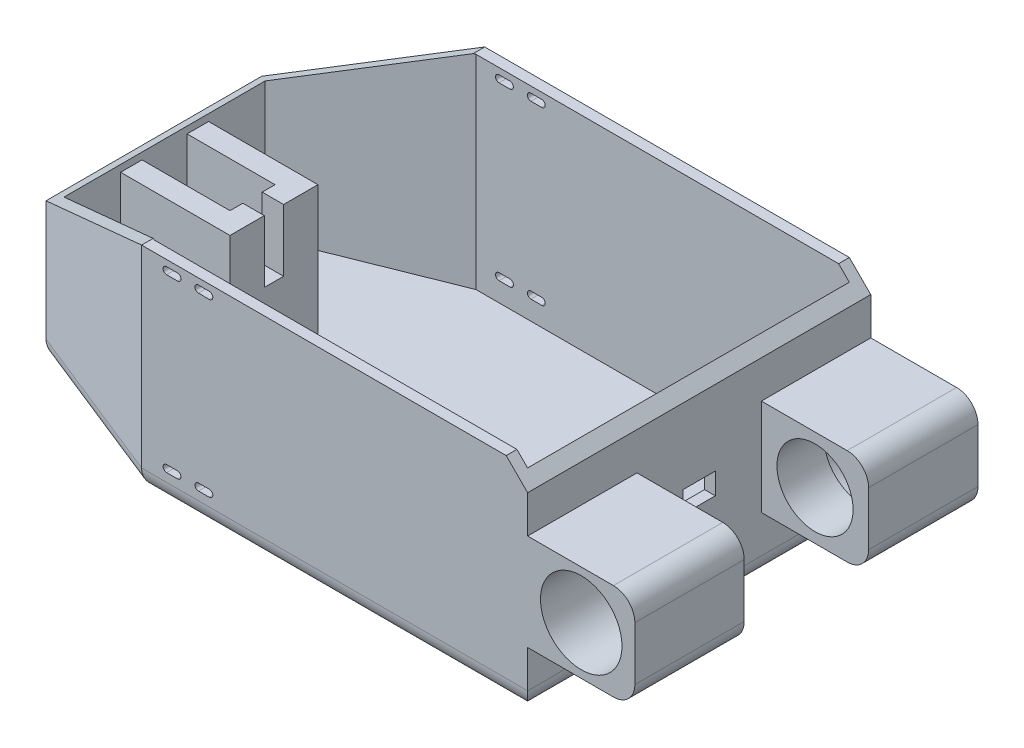
SolidWorks part; units mm, degrees
material "Silicon"
ref_plane "Front Plane" through (0, 0, 0) normal (0, 0, 1) x (1, 0, 0)
ref_plane "Top Plane" through (0, 0, 0) normal (0, 1, 0) x (1, 0, 0)
ref_plane "Right Plane" through (0, 0, 0) normal (1, 0, 0) x (0, 0, -1)
sketch "Sketch2" plane through (0, 0, 0) normal (0, 1, 0) x (1, 0, 0)
  line L0 (-11.9102, -80) -> (-11.9102, 80)
  line L1 (-11.9102, 0) -> (-266.1883, 0) construction
  line L2 (-11.9102, 0) -> (-191.9102, 0) construction
  line L4 (-191.9102, 80) -> (-11.9102, 80)
  line L5 (-11.9102, -80) -> (-191.9102, -80)
  line L6 (-266.1883, -50.2887) -> (-266.1883, 50.2887)
  line L9 (-266.1883, 50.2887) -> (-191.9102, 80)
  line L10 (-266.1883, -50.2887) -> (-191.9102, -80)
  point P3 (-11.9102, 0)
  point P10 (-191.9102, 0)
  point P13 (-266.1883, 0)
extrude "Boss-Extrude1" add sketch "Sketch2" along normal blind 100
shell "Shell1" thickness 5 removed face at (-156.6696, 100, 0)
chamfer "Chamfer1" distance 10 angle 45 1 edges at (-11.9102, 100, 0)
chamfer "Chamfer2" distance 10 angle 45 1 edges at (-266.1883, 100, 0)
fillet "Fillet2" radius 10 6 edges at (-11.9102, 0, 0) (-101.9102, 0, -80) (-229.0493, 0, -65.1444) (-266.1883, 0, 0) (-229.0493, 0, 65.1444) (-101.9102, 0, 80)
sketch "Sketch3" plane through (0, 0, 80) normal (0, 0, 1) x (1, 0, 0)
  line L0 (-191.9102, 100) -> (-266.1883, 65.8911)
  line L1 (-266.1883, 90) -> (-266.1883, 10) construction
  line L2 (-266.1883, 65.8911) -> (-266.1883, 100)
  line L3 (-266.1883, 100) -> (-191.9102, 100)
extrude "Cut-Extrude1" cut sketch "Sketch3" against normal blind 250
sketch "Sketch4" plane through (0, 5, 0) normal (0, 1, 0) x (1, 0, 0)
  line L1 (-261.1883, 46.9036) -> (-261.1883, -46.9036) construction
  line L2 (-261.1883, 10.5) -> (-220.1883, 10.5)
  line L3 (-220.1883, 10.5) -> (-220.1883, -10.5)
  line L4 (-220.1883, -10.5) -> (-384.7778, -10.5)
  line L5 (-215.1883, -15.5) -> (-444.0517, -15.5)
  line L7 (-261.6101, 15.5) -> (-215.1883, 15.5)
  line L8 (-215.1883, 15.5) -> (-215.1883, -15.5)
  line L9 (-384.7778, -10.5) -> (-261.1883, 10.5) construction
  line L10 (-261.1883, 10.5) -> (-384.7778, 9.5024)
  line L11 (-384.7778, 9.5024) -> (-384.7778, -10.5)
  line L12 (-261.6101, 15.5) -> (-444.0517, 15.5)
  line L13 (-444.0517, -15.5) -> (-261.6101, 15.5) construction
  line L14 (-444.0517, 15.5) -> (-444.0517, -15.5)
  point P5 (-336.9102, 0)
  dimension "D2" = 41
  dimension "D3" = 21
extrude "Boss-Extrude5" add sketch "Sketch4" along normal blind 60
sketch "Sketch8" plane through (0, 5, 0) normal (0, 1, 0) x (1, 0, 0)
  line L1 (-220.1883, 10.5) -> (-261.1883, 10.5)
  line L2 (-220.1883, 10.5) -> (-220.1883, -10.5)
  line L3 (-220.1883, -10.5) -> (-261.1883, -10.5)
  line L4 (-261.1883, 10.5) -> (-261.1883, -10.5)
  line L5 (-220.1883, 10.5) -> (-261.1883, -10.5) construction
  line L6 (-220.1883, -10.5) -> (-261.1883, 10.5) construction
  point P4 (-240.6883, 0)
extrude "Boss-Extrude6" add sketch "Sketch8" along normal blind 31
sketch "Sketch12" plane through (-11.9102, 0, 0) normal (1, 0, 0) x (0, 0, -1)
  line L0 (0, 90) -> (0, 10) construction
  line L1 (80, 90) -> (-80, 90) construction
  line L2 (-80, 10) -> (80, 10) construction
  line L3 (-80, 50) -> (80, 50) construction
  line L4 (80, 90) -> (80, 10) construction
  line L5 (-80, 27.5) -> (-80, 72.5)
  line L6 (-80, 90) -> (-80, 10) construction
  line L7 (-80, 72.5) -> (-29, 72.5)
  line L8 (-29, 72.5) -> (-29, 27.5)
  line L9 (-29, 27.5) -> (-80, 27.5)
  point P11 (0, 50)
  point P16 (-80, 50)
  dimension "D1" = 51
  dimension "D2" = 45
extrude "Boss-Extrude7" add sketch "Sketch12" along normal blind 50
sketch "Sketch26" plane through (0, 0, 80) normal (0, 0, 1) x (1, 0, 0)
  line L0 (13.0898, 27.5) -> (13.0898, 72.5) construction
  line L1 (38.0898, 27.5) -> (-11.9102, 27.5) construction
  line L2 (38.0898, 72.5) -> (-11.9102, 72.5) construction
  line L3 (-11.9102, 50) -> (38.0898, 50) construction
  line L4 (38.0898, 72.5) -> (38.0898, 27.5) construction
  circle A0 centre (13.0898, 50) radius 19
  point P11 (13.0898, 50)
  dimension "D1" = 38
extrude "Cut-Extrude2" cut sketch "Sketch26" against normal blind 29
sketch "Sketch28" plane through (0, 0, 51) normal (0, 0, 1) x (1, 0, 0)
  line L0 (13.0898, 72.5) -> (13.0898, 27.5) construction
  line L1 (38.0898, 72.5) -> (-11.9102, 72.5) construction
  line L2 (38.0898, 27.5) -> (-11.9102, 27.5) construction
  line L3 (-11.9102, 50) -> (38.0898, 50) construction
  line L4 (38.0898, 72.5) -> (38.0898, 27.5) construction
  circle A0 centre (13.0898, 50) radius 17.75
  point P11 (13.0898, 50)
  dimension "D1" = 35.5
extrude "Cut-Extrude3" cut sketch "Sketch28" against normal blind 22
mirror "Mirror1" about plane through (0, 0, 0) normal (0, 0, 1) of "Cut-Extrude3", "Cut-Extrude2", "Boss-Extrude7"
sketch "Sketch29" plane through (0, 65, 0) normal (0, 1, 0) x (1, 0, 0)
  line L0 (-261.1883, 20.5) -> (-210.1883, 20.5)
  line L1 (-210.1883, 20.5) -> (-210.1883, -20.5)
  line L2 (-210.1883, -20.5) -> (-261.1883, -20.5)
  line L3 (-261.1883, 20.5) -> (-261.1883, 15.5)
  line L4 (-261.1883, -15.5) -> (-261.1883, -20.5)
  line L16 (-261.1883, 15.5) -> (-215.1883, 15.5)
  line L17 (-215.1883, 15.5) -> (-215.1883, -15.5)
  line L18 (-215.1883, -15.5) -> (-261.1883, -15.5)
  dimension "D1" = 5
extrude "Boss-Extrude8" add sketch "Sketch29" against normal blind 60
sketch "Sketch30" plane through (0, 65, 0) normal (0, 1, 0) x (1, 0, 0)
  line L0 (-210.1883, -20.5) -> (-210.1883, 20.5) construction
  line L1 (-220.6883, -4.5) -> (-210.1883, -4.5)
  line L2 (-220.6883, -4.5) -> (-220.6883, 4.5)
  line L3 (-220.6883, 4.5) -> (-210.1883, 4.5)
  line L4 (-210.1883, -4.5) -> (-210.1883, 4.5)
  line L5 (-220.6883, -4.5) -> (-210.1883, 4.5) construction
  line L6 (-220.6883, 4.5) -> (-210.1883, -4.5) construction
  point P0 (-215.4383, 0)
  dimension "D1" = 10.5
  dimension "D2" = 9
extrude "Cut-Extrude4" cut sketch "Sketch30" against normal blind 29
fillet "Fillet4" radius 10 4 edges at (38.0898, 27.5, 54.5) (38.0898, 27.5, -54.5) (38.0898, 72.5, -54.5) (38.0898, 72.5, 54.5)
sketch "Sketch32" plane through (-11.9102, 0, 0) normal (1, 0, 0) x (0, 0, -1)
  line L0 (0, 90) -> (0, 10) construction
  line L1 (80, 90) -> (-80, 90) construction
  line L2 (-80, 10) -> (80, 10) construction
  line L3 (-80, 50) -> (80, 50) construction
  line L4 (80, 62.5) -> (80, 37.5) construction
  line L11 (-7.5, 45) -> (7.5, 45)
  line L17 (-7.5, 45) -> (-7.5, 55)
  line L18 (-7.5, 55) -> (7.5, 55)
  line L19 (7.5, 45) -> (7.5, 55)
  line L20 (-7.5, 45) -> (7.5, 55) construction
  line L21 (-7.5, 55) -> (7.5, 45) construction
  point P6 (0, 50)
  point P11 (0, 50)
  dimension "D1" = 15
  dimension "D2" = 10
extrude "Cut-Extrude7" cut sketch "Sketch32" against normal blind 10
sketch "Sketch34" plane through (0, 0, -80) normal (0, 0, -1) x (-1, 0, 0)
  line L0 (175.1622, 97.1086) -> (180.2505, 97.1086)
  line L1 (180.2505, 93.8517) -> (175.1622, 93.8517)
  line L2 (160.3185, 97.1086) -> (165.4019, 97.1086)
  line L3 (165.4019, 93.8517) -> (160.3185, 93.8517)
  line L4 (175.1609, 17.2037) -> (180.2409, 17.2037)
  line L5 (180.2409, 13.9537) -> (175.1609, 13.9537)
  line L6 (160.3242, 17.2037) -> (165.4042, 17.2037)
  line L7 (165.4042, 13.9537) -> (160.3242, 13.9537)
  arc A0 (180.2505, 97.1086) -> (180.2505, 93.8517) centre (180.2505, 95.4802) cw
  arc A1 (175.1622, 93.8517) -> (175.1622, 97.1086) centre (175.1622, 95.4802) cw
  arc A2 (165.4019, 97.1086) -> (165.4019, 93.8517) centre (165.4019, 95.4802) cw
  arc A3 (160.3185, 93.8517) -> (160.3185, 97.1086) centre (160.3185, 95.4802) cw
  arc A4 (180.2409, 17.2037) -> (180.2409, 13.9537) centre (180.2409, 15.5787) cw
  arc A5 (175.1609, 13.9537) -> (175.1609, 17.2037) centre (175.1609, 15.5787) cw
  arc A6 (165.4042, 17.2037) -> (165.4042, 13.9537) centre (165.4042, 15.5787) cw
  arc A7 (160.3242, 13.9537) -> (160.3242, 17.2037) centre (160.3242, 15.5787) cw
extrude "Cut-Extrude8" cut sketch "Sketch34" against normal blind 10
mirror "Mirror2" about plane through (0, 0, 0) normal (0, 0, 1) of "Cut-Extrude8"
sketch "Sketch37" plane through (0, 65, 0) normal (0, 1, 0) x (1, 0, 0)
  line L0 (-266.1883, 15.5) -> (-266.1883, -15.5)
  line L1 (-266.1883, -15.5) -> (-444.0517, -15.5)
  line L2 (-444.0517, -15.5) -> (-444.0517, 15.5)
  line L3 (-444.0517, 15.5) -> (-266.1883, 15.5)
extrude "Cut-Extrude10" cut sketch "Sketch37" against normal blind 84
fillet "Fillet11" radius 10 2 edges at (-266.1883, 5, 13) (-266.1883, 5, -12.9798)
